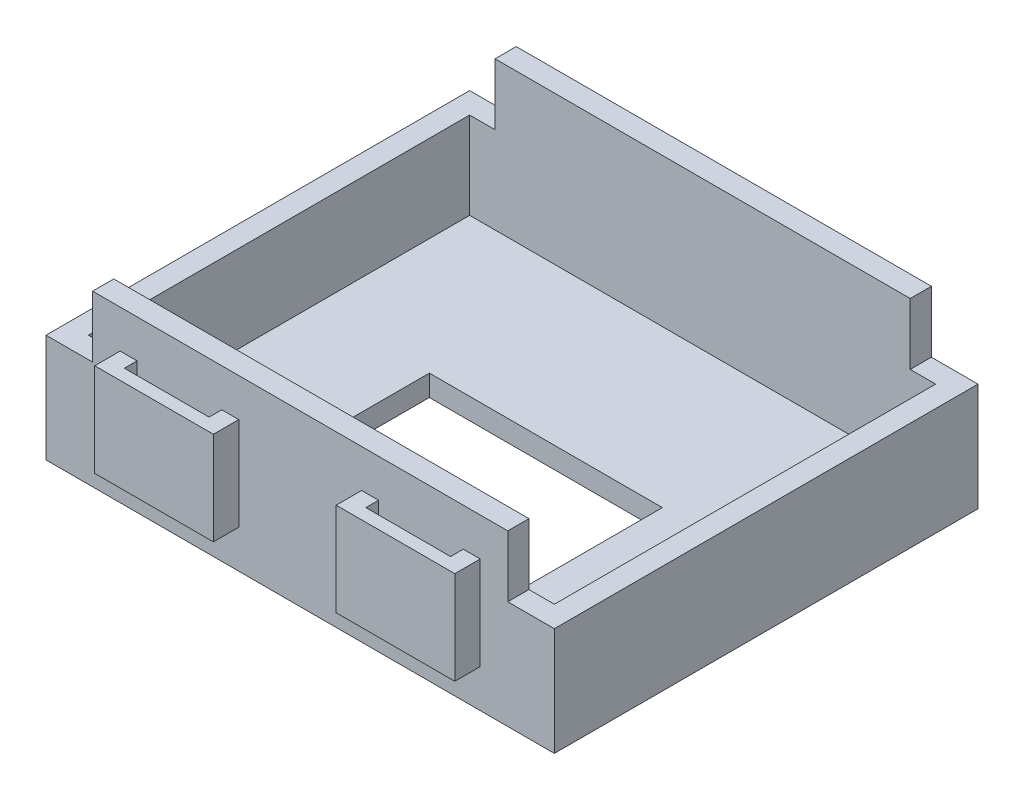
SolidWorks part; units mm, degrees
ref_plane "Front Plane" through (0, 0, 0) normal (0, 0, 1) x (1, 0, 0)
ref_plane "Top Plane" through (0, 0, 0) normal (0, 1, 0) x (1, 0, 0)
ref_plane "Right Plane" through (0, 0, 0) normal (1, 0, 0) x (0, 0, -1)
sketch "Croquis1" plane through (0, 0, 0) normal (0, 1, 0) x (1, 0, 0)
  line L1 (-30, 25) -> (30, 25)
  line L2 (-30, 25) -> (-30, -25)
  line L3 (-30, -25) -> (30, -25)
  line L4 (30, 25) -> (30, -25)
  line L5 (-30, 25) -> (30, -25) construction
  line L6 (-30, -25) -> (30, 25) construction
  point P0 (0, 0)
  dimension "D1" = 60
  dimension "D2" = 50
extrude "Saliente-Extruir1" add sketch "Croquis1" along normal blind 12.75
sketch "Croquis2" plane through (0, 0, 0) normal (0, 1, 0) x (1, 0, 0)
  line L0 (30, 25) -> (-30, 25) construction
  line L1 (-27.5, 22.5) -> (27.5, 22.5)
  line L2 (-27.5, 22.5) -> (-27.5, -22.5)
  line L3 (-27.5, -22.5) -> (27.5, -22.5)
  line L4 (27.5, 22.5) -> (27.5, -22.5)
  line L5 (-27.5, 22.5) -> (27.5, -22.5) construction
  line L6 (-27.5, -22.5) -> (27.5, 22.5) construction
  line L7 (-30, 25) -> (-30, -25) construction
  point P0 (0, 0)
  dimension "D1" = 2.5
  dimension "D2" = 2.5
extrude "Cortar-Extruir2" cut sketch "Croquis2" against normal blind 10.25 from surface starting at face at (0, 12.75, 0)
sketch "Croquis4" plane through (0, 0, 0) normal (0, 0, 1) x (1, 0, 0)
  line L0 (0, 0) -> (0, 12.75) construction
  line L1 (-30, 12.75) -> (30, 12.75) construction
  line L2 (-30, 12.75) -> (-24.5, 12.75) construction
  line L4 (30, 12.75) -> (24.5, 12.75) construction
  line L5 (-24.5, 12.75) -> (-24.5, 20)
  line L6 (-24.5, 20) -> (24.5, 20)
  line L7 (24.5, 20) -> (24.5, 12.75)
  line L8 (-30, 0) -> (30, 0) construction
  line L9 (-24.5, 12.75) -> (24.5, 12.75)
  dimension "D1" = 5.5
  dimension "D2" = 20
extrude "Saliente-Extruir2" add sketch "Croquis4" against normal blind 2.5 from surface starting at face at (0, 6.375, 25)
extrude "Saliente-Extruir3" add sketch "Croquis4<2>" along normal blind 2.5 from surface starting at face at (0, 6.375, -25)
sketch "Croquis4<2>" plane through (0, 0, 0) normal (0, 0, 1) x (1, 0, 0) same geometry as "Croquis4"
sketch "Croquis5" plane through (0, 0, 0) normal (0, 1, 0) x (1, 0, 0)
  line L0 (-13.75, -16) -> (13.75, -16)
  line L1 (13.75, -16) -> (13.75, 4)
  line L2 (13.75, 4) -> (-13.75, 4)
  line L3 (-13.75, 4) -> (-13.75, -16)
  line L4 (27.5, -22.5) -> (-27.5, -22.5) construction
  line L5 (27.5, 22.5) -> (27.5, -22.5) construction
  line L6 (-17, -16) -> (17, -16) construction
  line L7 (-17, -16) -> (-17, 16.15) construction
  line L8 (-17, 16.15) -> (17, 16.15) construction
  line L9 (17, -16) -> (17, 16.15) construction
  line L10 (-17, -16) -> (17, 16.15) construction
  line L11 (-17, 16.15) -> (17, -16) construction
  line L13 (-27.5, -22.5) -> (-27.5, 22.5) construction
  point P6 (0, 0.075)
  point P11 (0, 10.0799)
  dimension "D1" = 6.5
  dimension "D2" = 27.5
  dimension "D3" = 20
  dimension "D4" = 10.5
  dimension "D5" = 32.15
  dimension "D6" = 6.5
  dimension "D7" = 10.5
  dimension "D8" = 3.25
extrude "Cortar-Extruir3" cut sketch "Croquis5" along normal blind 10
sketch "Croquis6" plane through (0, 0, 0) normal (0, 0, 1) x (1, 0, 0)
  line L0 (0, 20) -> (0, 0) construction
  line L1 (24.5, 20) -> (-24.5, 20) construction
  line L2 (21.25, 4.5) -> (7.25, 15.5) construction
  line L3 (-21.25, 15.5) -> (-7.25, 15.5)
  line L4 (-21.25, 15.5) -> (-21.25, 4.5)
  line L5 (-21.25, 4.5) -> (-7.25, 4.5)
  line L6 (-7.25, 15.5) -> (-7.25, 4.5)
  line L7 (-21.25, 15.5) -> (-7.25, 4.5) construction
  line L8 (-21.25, 4.5) -> (-7.25, 15.5) construction
  line L9 (21.25, 15.5) -> (7.25, 4.5) construction
  line L10 (21.25, 15.5) -> (21.25, 4.5)
  line L11 (21.25, 4.5) -> (7.25, 4.5)
  line L12 (7.25, 15.5) -> (7.25, 4.5)
  line L13 (21.25, 15.5) -> (7.25, 15.5)
  line L14 (-30, 0) -> (30, 0) construction
  point P5 (-14.25, 10)
  point P14 (14.25, 10)
  dimension "D1" = 14.5
  dimension "D2" = 28.5
  dimension "D3" = 11
  dimension "D4" = 4.5
extrude "Saliente-Extruir5" add sketch "Croquis6" along normal blind 3 from surface starting at face at (0, 11.375, 25)
extrude "Saliente-Extruir6" add sketch "Croquis6<2>" against normal blind 3 from surface starting at face at (0, 11.375, -25)
sketch "Croquis6<2>" plane through (0, 0, 0) normal (0, 0, 1) x (1, 0, 0) same geometry as "Croquis6"
sketch "Croquis8" plane through (0, 0, 0) normal (0, 1, 0) x (1, 0, 0)
  line L0 (-7.25, 28) -> (-21.25, 28) construction
  line L1 (-19.25, 26.5) -> (-9.25, 26.5)
  line L2 (-19.25, 26.5) -> (-19.25, 25)
  line L3 (-19.25, 25) -> (-9.25, 25)
  line L4 (-9.25, 26.5) -> (-9.25, 25)
  line L5 (-19.25, 26.5) -> (-9.25, 25) construction
  line L6 (-19.25, 25) -> (-9.25, 26.5) construction
  line L7 (-7.25, 25) -> (-21.25, 25) construction
  line L8 (-21.25, 28) -> (-21.25, 25) construction
  line L9 (-7.25, 28) -> (-7.25, 25) construction
  line L10 (0, 36.1415) -> (0, -36.0507) construction
  line L11 (9.0758, 0) -> (-9.25, 0) construction
  line L12 (9.25, 26.5) -> (9.25, 25)
  line L13 (19.25, 25) -> (9.25, 25)
  line L14 (19.25, 26.5) -> (19.25, 25)
  line L15 (19.25, 26.5) -> (9.25, 26.5)
  line L16 (19.25, -25) -> (9.25, -25)
  line L17 (9.25, -26.5) -> (9.25, -25)
  line L18 (19.25, -26.5) -> (9.25, -26.5)
  line L19 (19.25, -26.5) -> (19.25, -25)
  line L20 (-9.25, -26.5) -> (-9.25, -25)
  line L21 (-19.25, -25) -> (-9.25, -25)
  line L22 (-19.25, -26.5) -> (-19.25, -25)
  line L23 (-19.25, -26.5) -> (-9.25, -26.5)
  point P0 (-14.25, 25.75)
  dimension "D1" = 1.5
  dimension "D2" = 0
  dimension "D3" = 2
  dimension "D4" = 2
extrude "Cortar-Extruir5" cut sketch "Croquis8" along normal blind 43.5
sketch "Croquis9" plane through (0, 0, 0) normal (0, 1, 0) x (1, 0, 0)
  line L0 (27.5, -22.5) -> (-27.5, -22.5) construction
  line L1 (-24.5, -19.5) -> (-20.5, -19.5)
  line L2 (-24.5, -19.5) -> (-24.5, -10.75)
  line L3 (-24.5, -10.75) -> (-20.5, -10.75)
  line L4 (-20.5, -19.5) -> (-20.5, -10.75)
  line L5 (-24.5, -19.5) -> (-20.5, -10.75) construction
  line L6 (-24.5, -10.75) -> (-20.5, -19.5) construction
  line L7 (-27.5, -22.5) -> (-27.5, 22.5) construction
  line L8 (27.5, 22.5) -> (27.5, -22.5) construction
  line L9 (18.35, -19.5) -> (24.5, -19.5)
  line L10 (18.35, -19.5) -> (18.35, -13.5)
  line L11 (18.35, -13.5) -> (24.5, -13.5)
  line L12 (24.5, -19.5) -> (24.5, -13.5)
  line L13 (18.35, -19.5) -> (24.5, -13.5) construction
  line L14 (18.35, -13.5) -> (24.5, -19.5) construction
  point P0 (-22.5, -15.125)
  point P9 (21.425, -16.5)
  dimension "D1" = 4
  dimension "D2" = 8.75
  dimension "D3" = 3
  dimension "D4" = 3
  dimension "D5" = 3
  dimension "D6" = 3
  dimension "D7" = 6.15
  dimension "D8" = 6
extrude "Cortar-Extruir6" cut sketch "Croquis9" along normal blind 43.5
